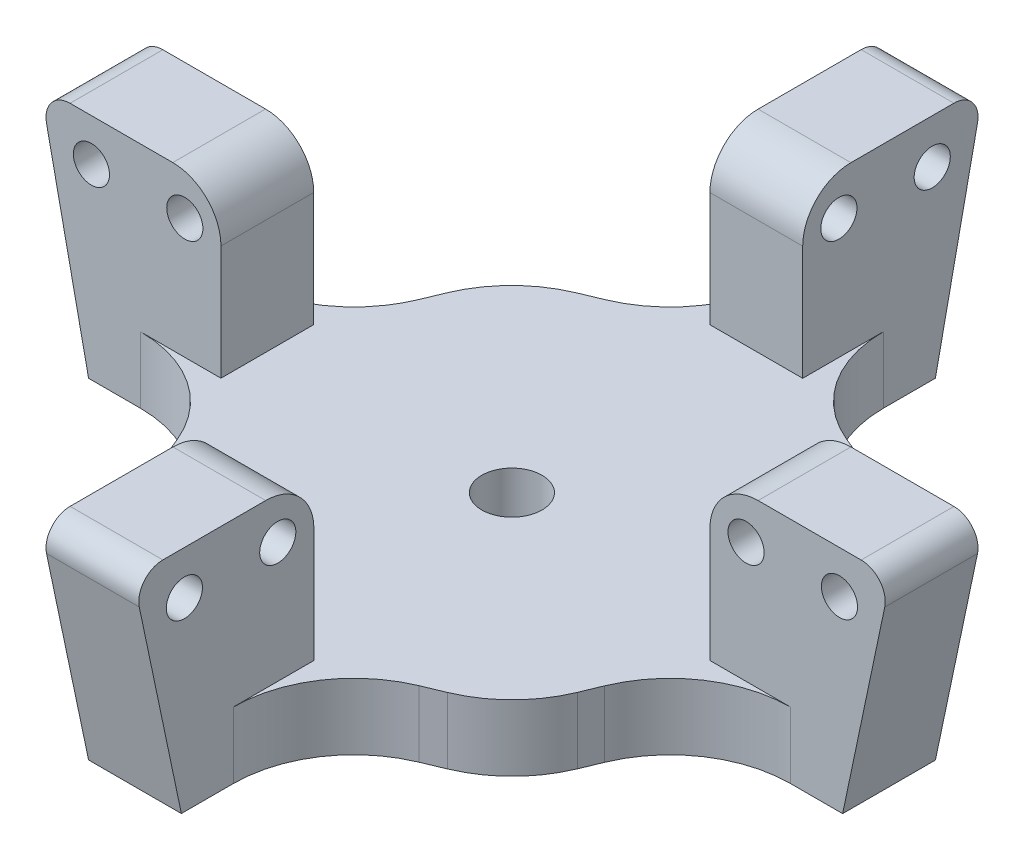
SolidWorks part; units mm, degrees
ref_plane "Piano frontale" through (0, 0, 0) normal (0, 0, 1) x (1, 0, 0)
ref_plane "Piano superiore" through (0, 0, 0) normal (0, 1, 0) x (1, 0, 0)
ref_plane "Piano destro" through (0, 0, 0) normal (1, 0, 0) x (0, 0, -1)
sketch "Schizzo1" plane through (0, 0, 0) normal (0, 1, 0) x (1, 0, 0)
  line L0 (0, 0) -> (0, 19.322) construction
  line L1 (0, 0) -> (0, -19.8246) construction
  line L2 (0, 0) -> (25.5113, 0) construction
  line L3 (0, 0) -> (-20.7358, 0) construction
  line L4 (-3.85, -20.284) -> (-3.85, -35.284)
  line L5 (15.4511, 15.5003) -> (3.85, 20.284)
  line L6 (-3.85, 20.2985) -> (-15.5003, 15.4511)
  line L7 (-15.5003, 15.4511) -> (-20.284, 3.85)
  line L8 (-20.2985, -3.85) -> (-15.4511, -15.5003)
  line L9 (-15.4511, -15.5003) -> (-3.85, -20.284)
  line L10 (3.85, -20.2985) -> (15.5003, -15.4511)
  line L11 (15.5003, -15.4511) -> (20.284, -3.85)
  line L12 (20.2985, 3.85) -> (15.4511, 15.5003)
  line L13 (-3.85, -35.284) -> (3.85, -35.284)
  line L14 (3.85, -35.284) -> (3.85, -20.2985)
  line L15 (-20.7358, 0) -> (-42.5055, 0) construction
  line L16 (0, 19.322) -> (0, 35.2985) construction
  line L17 (25.5113, 0) -> (43.1628, 0) construction
  line L18 (0.0348, -42.4551) -> (0, -19.8246) construction
  line L19 (-20.2985, -3.85) -> (-35.284, -3.85)
  line L20 (-35.284, -3.85) -> (-35.284, 3.85)
  line L21 (-35.284, 3.85) -> (-20.284, 3.85)
  line L22 (-3.85, 20.2985) -> (-3.85, 35.2985)
  line L23 (-3.85, 35.2985) -> (3.85, 35.2985)
  line L24 (3.85, 35.2985) -> (3.85, 20.284)
  line L25 (20.2985, 3.85) -> (35.2985, 3.85)
  line L26 (35.2985, 3.85) -> (35.2985, -3.85)
  line L27 (35.2985, -3.85) -> (20.284, -3.85)
  line L28 (0, 21.8716) -> (-0.0348, 21.8859)
  line L29 (-21.8716, 0) -> (-21.8859, -0.0348)
  line L30 (0.0031, -21.8729) -> (0.0348, -21.8859)
  line L31 (21.8716, 0) -> (21.8859, 0.0348)
  arc A1 (7.7675, -18.6685) -> (0.0006, -20.22) centre (0, 0) ccw construction
  dimension "D5" = 40.44
  dimension "D2" = 15
  dimension "D3" = 7.7
  dimension "D4" = 3.85
  dimension "D6" = 3.85
  dimension "D7" = 7.7
  dimension "D8" = 15
  dimension "D9" = 15
  dimension "D10" = 7.7
  dimension "D11" = 15
  dimension "D12" = 7.7
  dimension "D13" = 12.6185
extrude "Boss extrusion" add sketch "Schizzo1" along normal blind 5.5 contours L22 L23 L24 L5 L12 L25 L26 L27 L11 L10 L14 L13 L4 L9 L8 L19 L20 L21 L7 L6
sketch "Schizzo2" plane through (0, 5.5, 0) normal (0, 1, 0) x (1, 0, 0)
  line L0 (-3.85, -35.284) -> (3.85, -35.284) construction
  line L1 (-35.284, 3.85) -> (-20.2985, 3.85)
  line L2 (-35.284, 3.85) -> (-35.284, -3.85)
  line L3 (-35.284, -3.85) -> (-20.2985, -3.85)
  line L4 (-20.2985, 3.85) -> (-20.2985, -3.85)
  line L5 (-3.85, 35.2985) -> (3.85, 35.2985)
  line L6 (-3.85, 35.2985) -> (-3.85, 20.284)
  line L7 (-3.85, 20.284) -> (3.85, 20.284)
  line L8 (3.85, 35.2985) -> (3.85, 20.284)
  line L9 (35.2985, 3.85) -> (20.284, 3.85)
  line L10 (35.2985, 3.85) -> (35.2985, -3.85)
  line L11 (35.2985, -3.85) -> (20.284, -3.85)
  line L12 (20.284, 3.85) -> (20.284, -3.85)
  line L13 (-3.85, -20.284) -> (3.85, -20.284)
  line L14 (-3.85, -20.284) -> (-3.85, -35.284)
  line L15 (-3.85, -35.284) -> (3.85, -35.284)
  line L16 (3.85, -20.284) -> (3.85, -35.284)
  line L17 (3.85, -35.284) -> (3.85, -20.2985) construction
extrude "external extrusion" add sketch "Schizzo2" along normal blind 13.5
sketch "Schizzo3" plane through (0, 5.5, 0) normal (0, 1, 0) x (1, 0, 0)
  circle A0 centre (0, 0) radius 2.5
  dimension "D1" = 5
extrude "cetral hole" cut sketch "Schizzo3" against normal through all
sketch "Schizzo4" plane through (0, 0, 3.85) normal (0, 0, 1) x (1, 0, 0)
  line L0 (35.2985, 0) -> (35.2985, 19)
  line L1 (35.2985, 19) -> (31.2985, 0)
  line L2 (35.2985, 0) -> (20.284, 0) construction
  line L3 (31.2985, 0) -> (35.2985, 0)
  dimension "D1" = 4
extrude "Taglio-Estrusione2" cut sketch "Schizzo4" against normal through all
sketch "Schizzo5" plane through (3.85, 0, 0) normal (1, 0, 0) x (0, 0, -1)
  line L0 (35.2985, 0) -> (35.2985, 19)
  line L1 (35.2985, 19) -> (31.2985, 0)
  line L2 (35.2985, 0) -> (20.284, 0) construction
  line L3 (31.2985, 0) -> (35.2985, 0)
  dimension "D1" = 4
extrude "Taglio-Estrusione3" cut sketch "Schizzo5" against normal through all
sketch "Schizzo8" plane through (0, 0, -3.85) normal (0, 0, -1) x (-1, 0, 0)
  line L0 (35.284, 0) -> (35.284, 19)
  line L1 (35.284, 19) -> (31.284, 0)
  line L2 (35.284, 0) -> (20.284, 0) construction
  line L3 (31.284, 0) -> (35.284, 0)
  dimension "D1" = 4
extrude "Taglio-Estrusione4" cut sketch "Schizzo8" against normal through all
sketch "Schizzo9" plane through (-3.85, 0, 0) normal (-1, 0, 0) x (0, 0, 1)
  line L0 (35.284, 0) -> (35.284, 19)
  line L1 (35.284, 19) -> (31.284, 0)
  line L2 (20.284, 0) -> (35.284, 0) construction
  line L3 (31.284, 0) -> (35.284, 0)
  dimension "D1" = 4
extrude "Taglio-Estrusione5" cut sketch "Schizzo9" against normal through all
sketch "Schizzo10" plane through (-3.85, 0, 0) normal (-1, 0, 0) x (0, 0, 1)
  line L0 (20.284, 19) -> (20.284, 5.5) construction
  line L1 (20.284, 19) -> (35.284, 19) construction
  point P0 (23.284, 15.5)
  point P2 (31.034, 15.382)
  dimension "D1" = 3
  dimension "D2" = 3.5
  dimension "D3" = 7.75
hole_wizard "Foro per Vite M4-1" positions "Schizzo10" profile "Schizzo11" hole size "M4" standard "ISO" end condition through all
sketch "Schizzo11" plane through (-3.85, 15.5, 23.284) normal (0, 1, 0) x (0, 0, 1)
  line L0 (0, 0) -> (0, 39.1485)
  line L1 (0, 39.1485) -> (1.5, 39.1485)
  line L2 (1.5, 39.1485) -> (1.5, 0)
  line L5 (1.5, 0) -> (0, 0)
  line L11 (0, -6.35) -> (0, 107.95) construction
  dimension "Thru Hole Dia." = 3
  dimension "Thru Hole Depth" = 39.1485
sketch "Schizzo12" plane through (0, 0, 3.85) normal (0, 0, 1) x (1, 0, 0)
  line L0 (20.284, 19) -> (20.284, 5.5) construction
  line L1 (20.284, 19) -> (35.2985, 19) construction
  point P0 (23.284, 15.5)
  point P2 (31.034, 15.4693)
  dimension "D1" = 3
  dimension "D2" = 3.5
  dimension "D3" = 7.75
hole_wizard "Foro per Vite M4-2" positions "Schizzo12" profile "Schizzo13" hole size "M4" standard "ISO" end condition through all
sketch "Schizzo13" plane through (23.284, 15.5, 3.85) normal (1, 0, 0) x (0, -1, 0)
  line L0 (0, 0) -> (0, 39.1485)
  line L1 (0, 39.1485) -> (1.5, 39.1485)
  line L2 (1.5, 39.1485) -> (1.5, 0)
  line L5 (1.5, 0) -> (0, 0)
  line L11 (0, -6.35) -> (0, 107.95) construction
  dimension "Thru Hole Dia." = 3
  dimension "Thru Hole Depth" = 39.1485
sketch "Schizzo14" plane through (3.85, 0, 0) normal (1, 0, 0) x (0, 0, -1)
  line L0 (20.284, 19) -> (20.284, 5.5) construction
  line L1 (20.284, 19) -> (35.2985, 19) construction
  point P0 (23.284, 15.5)
  point P2 (31.034, 15.3152)
  dimension "D1" = 3
  dimension "D2" = 3.5
  dimension "D3" = 7.75
hole_wizard "Foro per Vite M4-3" positions "Schizzo14" profile "Schizzo15" hole size "M4" standard "ISO" end condition through all
sketch "Schizzo15" plane through (3.85, 15.5, -23.284) normal (0, 1, 0) x (0, 0, -1)
  line L0 (0, 0) -> (0, 39.134)
  line L1 (0, 39.134) -> (1.5, 39.134)
  line L2 (1.5, 39.134) -> (1.5, 0)
  line L5 (1.5, 0) -> (0, 0)
  line L11 (0, -6.35) -> (0, 107.95) construction
  dimension "Thru Hole Dia." = 3
  dimension "Thru Hole Depth" = 39.134
sketch "Schizzo16" plane through (0, 0, -3.85) normal (0, 0, -1) x (-1, 0, 0)
  line L0 (20.2985, 19) -> (20.2985, 5.5) construction
  line L1 (20.2985, 19) -> (35.284, 19) construction
  point P0 (23.2985, 15.5)
  point P2 (31.0485, 15.5)
  dimension "D1" = 3
  dimension "D2" = 7.75
  dimension "D3" = 3.5
hole_wizard "Foro per Vite M4-4" positions "Schizzo16" profile "Schizzo17" hole size "M4" standard "ISO" end condition through all
sketch "Schizzo17" plane through (-23.2985, 15.5, -3.85) normal (1, 0, 0) x (0, 1, 0)
  line L0 (0, 0) -> (0, 39.134)
  line L1 (0, 39.134) -> (1.5, 39.134)
  line L2 (1.5, 39.134) -> (1.5, 0)
  line L5 (1.5, 0) -> (0, 0)
  line L11 (0, -6.35) -> (0, 107.95) construction
  dimension "Thru Hole Dia." = 3
  dimension "Thru Hole Depth" = 39.134
fillet "Raccordo1" radius 4 1 edges at (20.284, 19, 0) type face fillet first side face at (20.284, 12.25, 0) second side face at (27.7913, 19, 0)
fillet "Raccordo2" radius 4 1 edges at (0, 19, -20.284) type face fillet first side face at (0, 12.25, -20.284) second side face at (0, 19, -27.7913)
fillet "Raccordo3" radius 4 1 edges at (-20.2985, 19, 0) type face fillet first side face at (-20.2985, 12.25, 0) second side face at (-27.7913, 19, 0)
fillet "Raccordo4" radius 4 1 edges at (0, 19, 20.284) type face fillet first side face at (0, 12.25, 20.284) second side face at (0, 19, 27.784)
fillet "Raccordo5" radius 2 1 edges at (-35.284, 19, 0) type face fillet first side face at (-33.284, 9.5, 0) second side face at (-29.7913, 19, 0)
fillet "Raccordo6" radius 2 1 edges at (0, 19, -35.2985) type face fillet first side face at (0, 19, -29.7913) second side face at (0, 9.5, -33.2985)
fillet "Raccordo7" radius 2 1 edges at (35.2985, 19, 0) type face fillet first side face at (33.2985, 9.5, 0) second side face at (29.7913, 19, 0)
fillet "Raccordo8" radius 2 1 edges at (0, 19, 35.284) type face fillet first side face at (0, 9.5, 33.284) second side face at (0, 19, 29.784)
fillet "Raccordo9" radius 10 1 edges at (3.85, 2.75, 20.2985) type face fillet first side face at (3.85, 15.5, 24.784) second side face at (9.6752, 2.75, 17.8748)
fillet "Raccordo17" radius 10 1 edges at (-3.85, 2.75, 20.284) type face fillet first side face at (-3.85, 15.5, 24.784) second side face at (-9.6505, 2.75, 17.8922)
fillet "Raccordo18" radius 10 1 edges at (20.284, 2.75, 3.85) type face fillet first side face at (17.8922, 2.75, 9.6505) second side face at (24.784, 15.5, 3.85)
fillet "Raccordo19" radius 10 1 edges at (20.2985, 2.75, -3.85) type face fillet first side face at (21.784, 15.5, -3.85) second side face at (17.8748, 2.75, -9.6752)
fillet "Raccordo20" radius 10 1 edges at (3.85, 2.75, -20.284) type face fillet first side face at (9.6505, 2.75, -17.8922) second side face at (3.85, 15.5, -24.784)
fillet "Raccordo21" radius 10 1 edges at (-3.85, 2.75, -20.2985) type face fillet first side face at (-3.85, 15.5, -21.784) second side face at (-9.6752, 2.75, -17.8748)
fillet "Raccordo22" radius 10 1 edges at (-20.284, 2.75, -3.85) type face fillet first side face at (-17.8922, 2.75, -9.6505) second side face at (-24.7985, 15.5, -3.85)
fillet "Raccordo23" radius 10 1 edges at (-20.2985, 2.75, 3.85) type face fillet first side face at (-21.7985, 15.5, 3.85) second side face at (-17.8748, 2.75, 9.6752)
fillet "Raccordo24" radius 10 1 edges at (-15.4511, 2.75, 15.5003)
fillet "Raccordo25" radius 10 3 edges at (-15.5003, 2.75, -15.4511) (15.4511, 2.75, -15.5003) (15.5003, 2.75, 15.4511)
